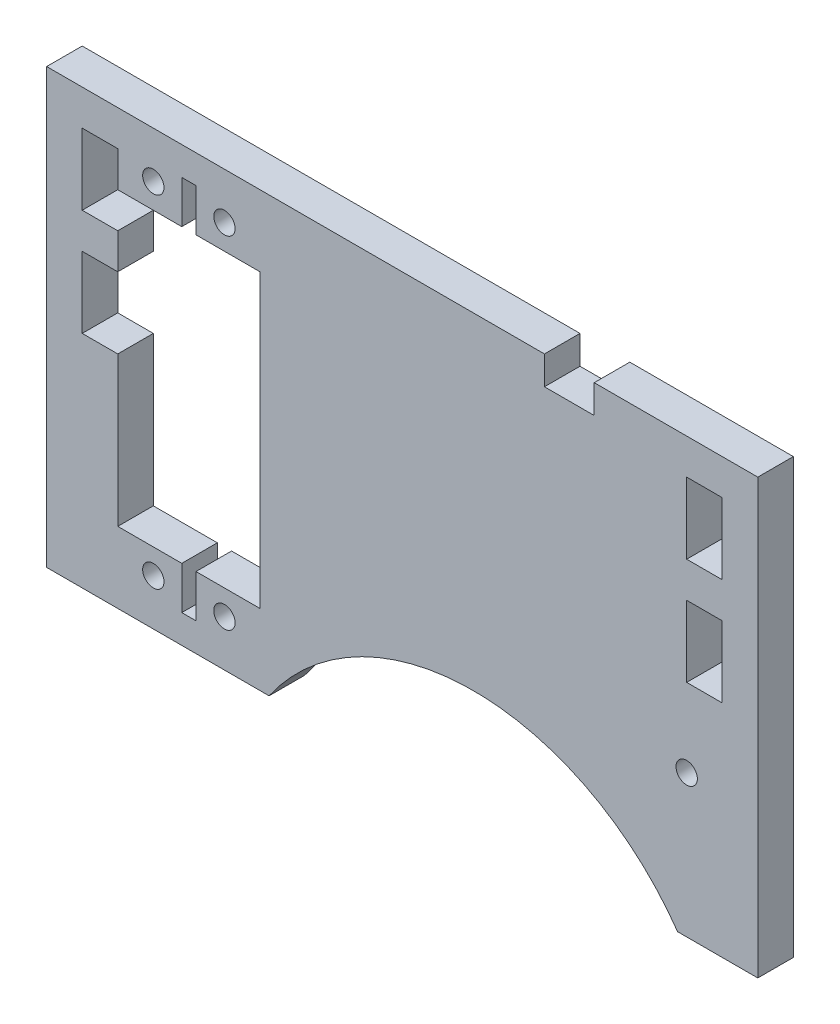
SolidWorks part; units mm, degrees
ref_plane "Plan de face" through (0, 0, 0) normal (0, 0, 1) x (1, 0, 0)
ref_plane "Plan de dessus" through (0, 0, 0) normal (0, 1, 0) x (1, 0, 0)
ref_plane "Plan de droite" through (0, 0, 0) normal (1, 0, 0) x (0, 0, -1)
sketch "Esquisse1" plane through (0, 0, 0) normal (0, 0, 1) x (1, 0, 0)
  line L0 (20, 71) -> (20, 0) construction
  line L1 (0, 0) -> (31.2772, 0)
  line L2 (0, 0) -> (0, 61)
  line L3 (0, 61) -> (70, 61)
  line L4 (100, 0) -> (100, 61)
  line L5 (10, 30.5) -> (30, 30.5) construction
  line L6 (10, 51) -> (19, 51)
  line L7 (10, 46) -> (10, 41)
  line L8 (10, 10) -> (19, 10)
  line L9 (30, 51) -> (30, 10)
  line L10 (20, 20) -> (90, 20) construction
  line L11 (88.7228, 0) -> (100, 0)
  line L12 (21, 4) -> (21, 10)
  line L13 (19, 57) -> (21, 57)
  line L14 (19, 57) -> (19, 51)
  line L15 (21, 10) -> (30, 10)
  line L16 (21, 57) -> (21, 51)
  line L17 (19, 4) -> (21, 4)
  line L18 (19, 4) -> (19, 10)
  line L19 (21, 51) -> (30, 51)
  line L20 (10, 31) -> (10, 10)
  line L21 (90, 56) -> (95, 56)
  line L22 (90, 56) -> (90, 46)
  line L23 (90, 46) -> (95, 46)
  line L24 (95, 56) -> (95, 46)
  line L25 (90, 41) -> (95, 41)
  line L26 (90, 41) -> (90, 31)
  line L27 (90, 31) -> (95, 31)
  line L28 (95, 41) -> (95, 31)
  line L29 (5, 56) -> (10, 56)
  line L30 (5, 56) -> (5, 46)
  line L31 (5, 46) -> (10, 46)
  line L32 (10, 56) -> (10, 51)
  line L33 (5, 41) -> (10, 41)
  line L34 (5, 41) -> (5, 31)
  line L35 (5, 31) -> (10, 31)
  line L36 (77, 61) -> (100, 61)
  line L38 (77, 61) -> (77, 57)
  line L39 (77, 57) -> (70, 57)
  line L40 (70, 61) -> (70, 57)
  circle A0 centre (15, 6.5) radius 1.5
  circle A1 centre (25, 6.5) radius 1.5
  circle A2 centre (25, 54.5) radius 1.5
  circle A3 centre (15, 54.5) radius 1.5
  circle A4 centre (20, 20) radius 1.5 construction
  circle A5 centre (20, 20) radius 1.5 construction
  circle A6 centre (90, 20) radius 1.5
  circle A7 centre (60, -20) radius 35 construction
  arc A8 (31.2772, 0) -> (88.7228, 0) centre (60, -20) cw
  dimension "D6" = 3.5
  dimension "D8" = 3
  dimension "D9" = 3
  dimension "D10" = 70
  dimension "D13" = 70
  dimension "D16" = 2
  dimension "D1" = 10
  dimension "D2" = 41
  dimension "D3" = 20
  dimension "D4" = 10
  dimension "D5" = 100
  dimension "D7" = 5
  dimension "D11" = 10
  dimension "D12" = 10
  dimension "D14" = 40
  dimension "D15" = 40
  dimension "D17" = 6
  dimension "D18" = 5
  dimension "D19" = 5
  dimension "D20" = 10
  dimension "D21" = 5
  dimension "D22" = 5
  dimension "D23" = 5
  dimension "D24" = 10
  dimension "D25" = 7
  dimension "D26" = 4
  dimension "D27" = 23
extrude "Boss.-Extru.1" add sketch "Esquisse1" along normal blind 5
